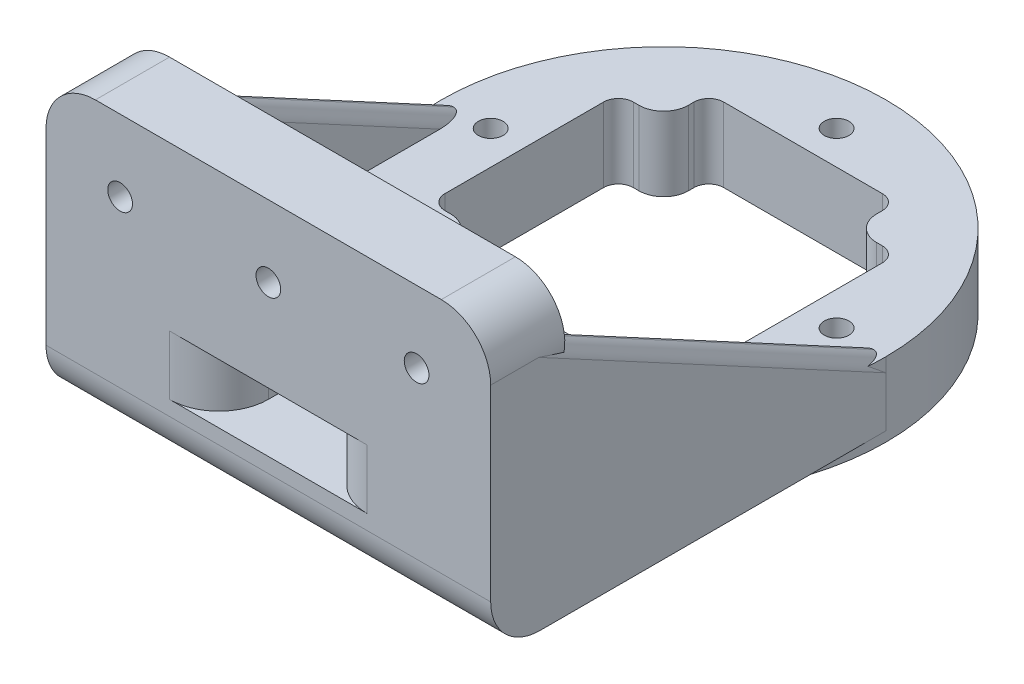
SolidWorks part; units mm, degrees
ref_plane "Front Plane" through (0, 0, 0) normal (0, 0, 1) x (1, 0, 0)
ref_plane "Top Plane" through (0, 0, 0) normal (0, 1, 0) x (1, 0, 0)
ref_plane "Right Plane" through (0, 0, 0) normal (1, 0, 0) x (0, 0, -1)
sketch "Sketch1" plane through (0, 0, 0) normal (0, 1, 0) x (1, 0, 0)
  line L0 (-16.05, 28.2) -> (16.05, 28.2)
  line L1 (-28.2, 16.05) -> (-28.2, -16.05)
  line L2 (-16.05, -28.2) -> (16.05, -28.2)
  line L3 (28.2, 16.05) -> (28.2, -16.05)
  line L4 (-25.2, 19.05) -> (-24.05, 19.05)
  line L5 (-19.05, 25.2) -> (-19.05, 24.05)
  line L6 (25.2, 19.05) -> (24.05, 19.05)
  line L7 (19.05, 25.2) -> (19.05, 24.05)
  line L8 (-24.05, -19.05) -> (-25.2, -19.05)
  line L9 (-19.05, -24.05) -> (-19.05, -25.2)
  line L10 (24.05, -19.05) -> (25.2, -19.05)
  line L11 (19.05, -24.05) -> (19.05, -25.2)
  line L12 (-45, -80) -> (45, -80)
  line L14 (-45, -80) -> (-45, 0)
  line L15 (-45, 0) -> (45, 0)
  line L16 (45, -80) -> (45, 0)
  line L17 (0, -45) -> (45, 0) construction
  line L18 (-45, 0) -> (0, -45) construction
  circle A0 centre (0, 0) radius 45
  arc A1 (24.05, 19.05) -> (19.05, 24.05) centre (24.05, 24.05) cw
  arc A2 (-24.05, 19.05) -> (-19.05, 24.05) centre (-24.05, 24.05) ccw
  arc A3 (-24.05, -19.05) -> (-19.05, -24.05) centre (-24.05, -24.05) cw
  arc A4 (19.05, -24.05) -> (24.05, -19.05) centre (24.05, -24.05) cw
  arc A5 (-28.2, 16.05) -> (-25.2, 19.05) centre (-25.2, 16.05) cw
  arc A6 (-28.2, -16.05) -> (-25.2, -19.05) centre (-25.2, -16.05) ccw
  arc A7 (-16.05, -28.2) -> (-19.05, -25.2) centre (-16.05, -25.2) cw
  arc A8 (16.05, -28.2) -> (19.05, -25.2) centre (16.05, -25.2) ccw
  arc A9 (25.2, -19.05) -> (28.2, -16.05) centre (25.2, -16.05) ccw
  arc A10 (28.2, 16.05) -> (25.2, 19.05) centre (25.2, 16.05) ccw
  arc A11 (16.05, 28.2) -> (19.05, 25.2) centre (16.05, 25.2) cw
  arc A12 (-19.05, 25.2) -> (-16.05, 28.2) centre (-16.05, 25.2) cw
  point P0 (0, 0)
  point P5 (0, 0)
  point P40 (0, -45)
  dimension "D2" = 90
  dimension "D3" = 5
  dimension "D4" = 3
  dimension "D1" = 28.2
  dimension "D5" = 32.1
  dimension "D6" = 32.1
  dimension "D7" = 80
extrude "Boss-Extrude1" add sketch "Sketch1" along normal blind 15 contours A0 L14 L12 L16 | A9 L10 A4 L11 A8 L2 A7 L9 A3 L8 A6 L1 L15 A0 L3 | L5 A12 L0 A11 L7 A1 L6 A10 L3 L15 A0 L1 A5 L4 A2 region at (-18.8828, 0, -28.0328) region at (-29.2062, 0, 8.025) region at (0, 0, 56.542)
sketch "Sketch2" plane through (0, 15, 0) normal (0, 1, 0) x (1, 0, 0)
  line L0 (45, -80) -> (45, 0) construction
  line L1 (-45, -80) -> (45, -80)
  line L2 (-45, -80) -> (-45, -65)
  line L3 (-45, -65) -> (45, -65)
  line L4 (45, -80) -> (45, -65)
  circle A0 centre (0, 0) radius 40
  line M27 (45, -80) -> (45, 0)
  line M29 (-45, 0) -> (-45, -80)
  line M30 (-45, -80) -> (45, -80)
  dimension "D1" = 80
  dimension "D3" = 15
extrude "Boss-Extrude2" add sketch "Sketch2" along normal blind 45 contours L3 M29 M30 M27 region at (0, 15, 72.5)
sketch "Sketch3" plane through (0, 0, 0) normal (0, -1, 0) x (-1, 0, 0)
  line L1 (45, -80) -> (-45, -80)
  line L2 (45, -80) -> (45, 0)
  line L4 (-45, -80) -> (-45, 0)
  arc A0 (-45, 0) -> (45, 0) centre (0, 0) ccw
extrude "Cut-Extrude1" cut sketch "Sketch3" against normal blind 2
sketch "Sketch4" plane through (0, 0, 0) normal (0, -1, 0) x (-1, 0, 0)
  circle A0 centre (0, 0) radius 35
  circle A1 centre (0, -35) radius 2.5
  circle A2 centre (-35, 0) radius 2.5
  circle A3 centre (0, 35) radius 2.5
  circle A4 centre (35, 0) radius 2.5
  point P14 (0, 0)
  dimension "D1" = 70
  dimension "D2" = 5
  dimension "D3" = 4
extrude "Cut-Extrude2" cut sketch "Sketch4" against normal through all contours A1 | A2 | A4 | A3
fillet "Fillet1" radius 10 4 edges at (-45, 60, 72.5) (45, 60, 72.5) (0, 15, 65) (0, 2, 80)
sketch "Sketch5" plane through (0, 0, 65) normal (0, 0, -1) x (-1, 0, 0)
  circle A0 centre (-30, 45.5029) radius 2.5
  circle A1 centre (30, 45.5029) radius 2.5
  circle A2 centre (0, 45.5029) radius 2.5
  dimension "D1" = 5
  dimension "D2" = 5
  dimension "D3" = 5
  dimension "D4" = 30
  dimension "D5" = 30
  dimension "D6" = 45.5029
extrude "Cut-Extrude3" cut sketch "Sketch5" against normal through all
sketch "Sketch6" plane through (0, 15, 0) normal (0, 1, 0) x (1, 0, 0)
  line L0 (15, -50) -> (-15, -50)
  line L1 (-15, -50) -> (15, -50) construction
  line L2 (-15, -47.5) -> (15, -47.5)
  line L3 (-15, -52.5) -> (15, -52.5)
  line L4 (-45, -55) -> (45, -55) construction
  arc A0 (-15, -47.5) -> (-15, -52.5) centre (-15, -50) ccw
  arc A1 (15, -52.5) -> (15, -47.5) centre (15, -50) ccw
  point P0 (0, -50)
  point P3 (0, -50)
  dimension "D2" = 2.5
  dimension "D1" = 30
  dimension "D3" = 5
extrude "Cut-Extrude4" cut sketch "Sketch6" against normal through all contours L3 A1 L2 A0 region at (0, 15, 47.8536)
sketch "Sketch7" plane through (0, 2, 0) normal (0, -1, 0) x (1, 0, 0)
  line L0 (-15, 50) -> (15, 50) construction
  line L1 (-15, 54) -> (15, 54)
  line L2 (-15, 46) -> (15, 46)
  arc A0 (-15, 54) -> (-15, 46) centre (-15, 50) ccw
  arc A1 (15, 46) -> (15, 54) centre (15, 50) ccw
  point P4 (0, 50)
  dimension "D1" = 4
extrude "Cut-Extrude5" cut sketch "Sketch7" against normal blind 4
sketch "Sketch8" plane through (0, 0, 65) normal (0, 0, -1) x (-1, 0, 0)
  line L1 (-10, 27) -> (10, 27)
  line L2 (-10, 27) -> (-10, 15)
  line L3 (-10, 15) -> (10, 15)
  line L4 (10, 27) -> (10, 15)
  line L6 (45, 15) -> (-45, 15) construction
  point P8 (0, 27)
  dimension "D1" = 20
  dimension "D2" = 12
extrude "Cut-Extrude6" cut sketch "Sketch8" against normal up to vertex (15 mm away) and the other way blind 10 up to point (45, 12, 80)
fillet "Fillet2" radius 10 2 edges at (-10, 21, 80) (10, 21, 80)
sketch "Sketch9" plane through (45, 0, 0) normal (1, 0, 0) x (0, 0, -1)
  line L0 (0, 15) -> (-65, 50)
  line L1 (-65, 50) -> (-65, 25)
  line L2 (-55, 15) -> (0, 15)
  arc A0 (-65, 25) -> (-55, 15) centre (-55, 25) ccw
extrude "Boss-Extrude3" add sketch "Sketch9" against normal blind 5
mirror "Mirror1" about plane through (0, 0, 0) normal (1, 0, 0) of "Boss-Extrude3"
fillet "Fillet4" radius 2.5 4 edges at (-45, 32.5, 32.5) (-40, 32.5, 32.5) (40, 32.5, 32.5) (45, 32.5, 32.5)
